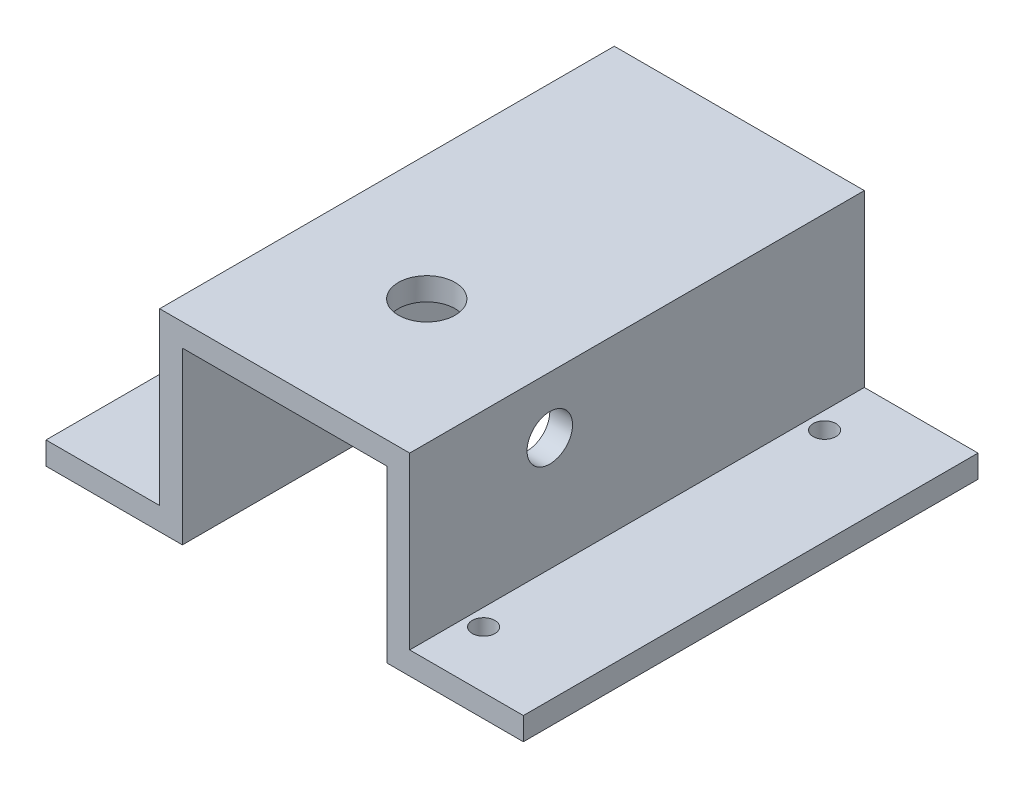
SolidWorks part; units mm, degrees
ref_plane "Front Plane" through (0, 0, 0) normal (0, 0, 1) x (1, 0, 0)
ref_plane "Top Plane" through (0, 0, 0) normal (0, 1, 0) x (1, 0, 0)
ref_plane "Right Plane" through (0, 0, 0) normal (1, 0, 0) x (0, 0, -1)
sketch "Sketch1" plane through (0, 0, 0) normal (0, 0, 1) x (1, 0, 0)
  line L0 (0, 35.148) -> (0, 32.945) construction
  line L1 (22, 32.945) -> (-22, 32.945)
  line L2 (-22, 32.945) -> (-22, 2.945)
  line L3 (-22, 2.945) -> (-42, 2.945)
  line L4 (-42, 2.945) -> (-42, -1.055)
  line L9 (-42, -1.055) -> (-18, -1.055)
  line L10 (-18, -1.055) -> (-18, 28.945)
  line L11 (-18, 28.945) -> (18, 28.945)
  line L12 (0, 28.945) -> (0, -27.5376) construction
  line L13 (18, -1.055) -> (18, 28.945)
  line L14 (42, -1.055) -> (18, -1.055)
  line L15 (42, 2.945) -> (42, -1.055)
  line L16 (22, 2.945) -> (42, 2.945)
  line L17 (22, 32.945) -> (22, 2.945)
  dimension "D1" = 22
  dimension "D2" = 30
  dimension "D3" = 4
  dimension "D4" = 20
  dimension "D5" = 4
  dimension "D6" = 4
extrude "Boss-Extrude1" add sketch "Sketch1" along normal blind 80
sketch "Sketch2" plane through (0, 2.945, 0) normal (0, 1, 0) x (1, 0, 0)
  line L0 (42, 0) -> (22, 0) construction
  line L1 (42, -80) -> (22, -80) construction
  line L2 (0, 20.067) -> (0, -78.6664) construction
  circle A0 centre (25, -10) radius 2
  circle A1 centre (25, -70) radius 2
  circle A2 centre (-25, -70) radius 2
  circle A3 centre (-25, -10) radius 2
  dimension "D1" = 4
  dimension "D2" = 4
  dimension "D3" = 10
  dimension "D4" = 10
extrude "Cut-Extrude1" cut sketch "Sketch2" against normal blind 70
sketch "Sketch3" plane through (0, 32.945, 0) normal (0, 1, 0) x (1, 0, 0)
  line L0 (22, -80) -> (-22, -80) construction
  circle A0 centre (0, -55) radius 5
  dimension "D2" = 10
  dimension "D1" = 25
extrude "Cut-Extrude2" cut sketch "Sketch3" against normal blind 70
sketch "Sketch4" plane through (-22, 0, 0) normal (-1, 0, 0) x (0, 0, 1)
  line L0 (55.3466, 32.945) -> (55.3466, 2.945) construction
  line L1 (80, 32.945) -> (0, 32.945) construction
  line L2 (80, 2.945) -> (0, 2.945) construction
  circle A0 centre (55.3466, 22.945) radius 4
  dimension "D2" = 8
  dimension "D1" = 10
extrude "Cut-Extrude3" cut sketch "Sketch4" against normal blind 70
